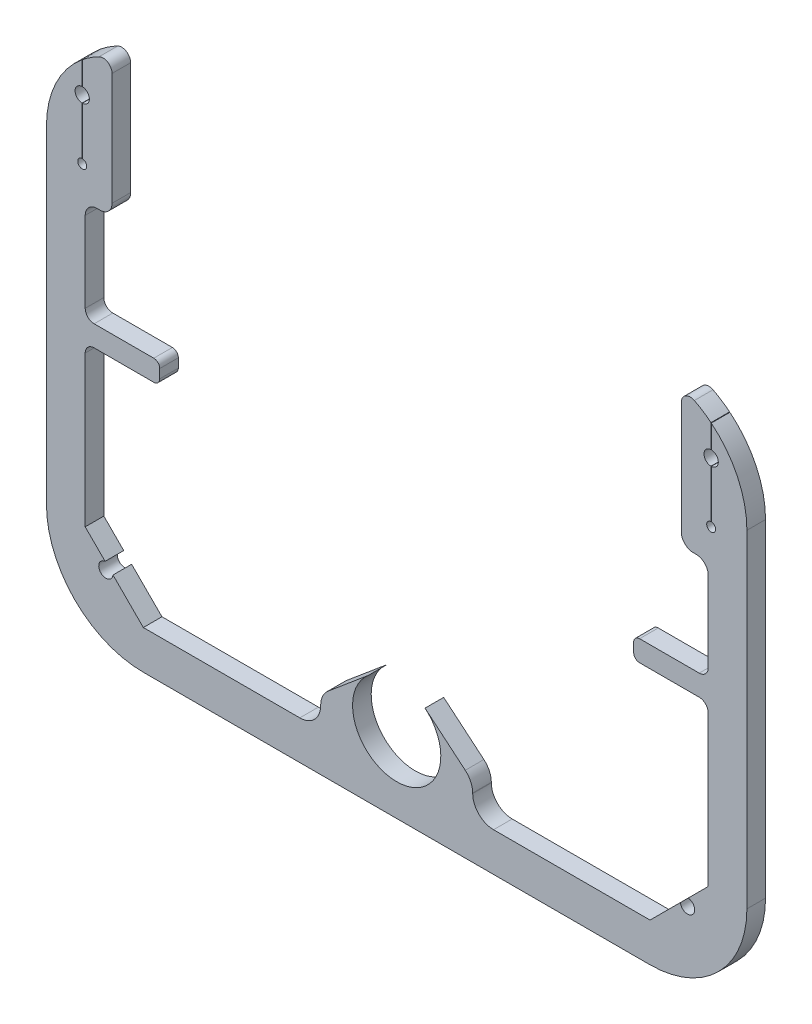
SolidWorks part; units mm, degrees
material "Delrin 2700 NC010, Low Viscosity Acetal Copolymer (SS)"
ref_plane "Front Plane" through (0, 0, 0) normal (0, 0, 1) x (1, 0, 0)
ref_plane "Top Plane" through (0, 0, 0) normal (0, 1, 0) x (1, 0, 0)
ref_plane "Right Plane" through (0, 0, 0) normal (1, 0, 0) x (0, 0, -1)
sketch "Sketch1" plane through (0, 0, 0) normal (0, 0, 1) x (1, 0, 0)
  line L0 (-21.59, -18.923) -> (-9.6321, -18.923)
  line L1 (21.59, 22.225) -> (-21.59, 22.225)
  line L2 (29.845, 13.97) -> (29.845, -13.97)
  line L3 (21.59, -22.225) -> (-21.59, -22.225)
  line L4 (-29.845, 13.97) -> (-29.845, -13.97)
  line L5 (29.845, 22.225) -> (-29.845, -22.225) construction
  line L6 (29.845, -22.225) -> (-29.845, 22.225) construction
  line L7 (9.6321, -18.923) -> (21.59, -18.923)
  line L8 (-26.543, -0.381) -> (-20.193, -0.381)
  line L9 (26.543, 1.397) -> (20.193, 1.397)
  line L10 (-26.543, 10.033) -> (-26.543, -13.97)
  line L11 (-1000, 0) -> (49000, 0) construction
  line L12 (-26.543, 0) -> (-26.543, -1.27)
  line L13 (26.543, 10.033) -> (26.543, -13.97)
  line L14 (21.59, 18.923) -> (-21.59, 18.923)
  line L15 (26.543, 1.397) -> (26.543, -0.381)
  line L16 (26.543, -0.381) -> (20.193, -0.381)
  line L17 (20.193, 1.397) -> (20.193, -0.381)
  line L18 (0, 18.923) -> (0, -18.415) construction
  line L19 (-20.193, 1.397) -> (-20.193, -0.381)
  line L20 (-26.543, 1.397) -> (-20.193, 1.397)
  line L21 (2.4164, -12.8683) -> (9.6321, -18.923)
  line L22 (-2.4164, -12.8683) -> (-9.6321, -18.923)
  line L23 (21.59, 18.923) -> (21.59, 10.033)
  line L24 (-21.59, 18.923) -> (-21.59, 10.033)
  line L25 (26.543, -13.97) -> (21.59, -18.923)
  line L26 (-21.59, 10.033) -> (-26.543, 10.033)
  line L27 (-26.543, -13.97) -> (-21.59, -18.923)
  line L28 (21.59, 10.033) -> (26.543, 10.033)
  line L29 (-26.543, 13.97) -> (-26.543, -13.97) construction
  line L31 (26.543, 13.97) -> (26.543, -13.97) construction
  line L36 (21.59, -18.923) -> (-21.59, -18.923) construction
  arc A0 (-2.4164, -12.8683) -> (2.4164, -12.8683) centre (0, -15.748) ccw
  arc A1 (-21.59, 22.225) -> (-29.845, 13.97) centre (-21.59, 13.97) ccw
  arc A2 (21.59, 22.225) -> (29.845, 13.97) centre (21.59, 13.97) cw
  arc A3 (29.845, -13.97) -> (21.59, -22.225) centre (21.59, -13.97) cw
  arc A4 (-21.59, -22.225) -> (-29.845, -13.97) centre (-21.59, -13.97) cw
  arc A13 (-21.59, -18.923) -> (-26.543, -13.97) centre (-21.59, -13.97) cw construction
  arc A14 (26.543, -13.97) -> (21.59, -18.923) centre (21.59, -13.97) cw construction
  arc A17 (21.59, 18.923) -> (26.543, 13.97) centre (21.59, 13.97) cw construction
  arc A18 (-21.59, 18.923) -> (-26.543, 13.97) centre (-21.59, 13.97) ccw construction
  point P0 (0, 0)
  dimension "D4" = 7.5184
  dimension "D6" = 8.255
  dimension "D7" = 8.255
  dimension "D8" = 8.255
  dimension "D9" = 8.255
  dimension "D5" = 8.89
  dimension "D1" = 59.69
  dimension "D2" = 44.45
  dimension "D10" = 3.302
  dimension "D3" = 3.175
  dimension "D13" = 15.748
  dimension "D14" = 1.778
  dimension "D15" = 21.844
  dimension "D16" = 6.35
extrude "Boss-Extrude1" add sketch "Sketch1" along normal blind 1.5875 contours A4 L3 A3 L2 A2 L1 A1 L4 L25 L7 L21 A0 L22 L0 L27 L10 L14 L13 | L9 L17 L16 L13 | L20 L10 L8 L19 region at (-23.368, 0.508, 0) region at (23.368, 0.508, 0) region at (26.9009, 19.2809, 0)
sketch "Sketch2" plane through (0, 0, 1.5875) normal (0, 0, 1) x (1, 0, 0)
  line L0 (-21.59, 10.033) -> (-26.543, 10.033) construction
  line L1 (-9.6321, -18.923) -> (-6.477, -18.923)
  line L2 (-9.6321, -18.923) -> (-9.6321, -16.2756)
  line L3 (-9.6321, -16.2756) -> (-6.477, -16.2756)
  line L4 (-6.477, -18.923) -> (-6.477, -16.2756)
  line L5 (0, -1000) -> (0, 49000) construction
  line L6 (9.6321, -18.923) -> (9.6321, -16.2756)
  line L7 (9.6321, -16.2756) -> (6.477, -16.2756)
  line L8 (6.477, -18.923) -> (6.477, -16.2756)
  line L9 (9.6321, -18.923) -> (6.477, -18.923)
  line L10 (-29.845, 13.97) -> (-29.845, -13.97) construction
  line L11 (-21.59, 18.923) -> (21.59, 18.923)
  line L12 (-24.257, 10.033) -> (-24.257, 22.225)
  line L13 (-24.257, 22.225) -> (24.257, 22.225)
  line L14 (24.257, 10.033) -> (24.257, 22.225)
  line L16 (21.59, 18.923) -> (-21.59, 18.923) construction
  line L17 (-2.4164, -12.8683) -> (-9.6321, -18.923) construction
  line L18 (21.59, 22.225) -> (-21.59, 22.225) construction
  line L19 (21.59, 18.923) -> (-21.59, 18.923) construction
  line L22 (-21.59, 18.923) -> (-21.59, 10.033) construction
  line L23 (21.59, 10.033) -> (26.543, 10.033) construction
  line L24 (21.59, 18.923) -> (21.59, 10.033) construction
  line L25 (-21.59, 18.923) -> (-21.59, 10.033)
  line L26 (-21.59, 10.033) -> (-24.257, 10.033)
  line L27 (21.59, 10.033) -> (24.257, 10.033)
  line L28 (21.59, 18.923) -> (21.59, 10.033)
  point P25 (0, 22.225)
  dimension "D1" = 6.477
  dimension "D2" = 5.588
extrude "Cut-Extrude1" cut sketch "Sketch2" against normal up to next
fillet "Fillet1" radius 1.778 4 edges at (6.477, -18.923, 0.7937) (6.477, -16.2756, 0.7937) (-6.477, -18.923, 0.7937) (-6.477, -16.2756, 0.7937)
fillet "Fillet2" radius 0.762 2 edges at (24.257, 21.7823, 0.7937) (-24.257, 21.7823, 0.7937)
fillet "Fillet3" radius 0.762 4 edges at (-26.543, -0.381, 0.7937) (26.543, -0.381, 0.7937) (26.543, 1.397, 0.7937) (-26.543, 1.397, 0.7937)
sketch "Sketch3" plane through (0, 0, 1.5875) normal (0, 0, 1) x (1, 0, 0)
  line L0 (-25.019, -16.51) -> (-24.7804, -16.2714) construction
  line L1 (21.59, -22.225) -> (-21.59, -22.225) construction
  line L2 (-26.543, -13.97) -> (-21.59, -18.923) construction
  line L3 (24.7804, -16.2714) -> (25.019, -16.51) construction
  circle A0 centre (-25.019, -16.51) radius 0.6096 construction
  circle A1 centre (-25.019, 16.256) radius 0.6096 construction
  circle A2 centre (25.019, 16.256) radius 0.6096 construction
  circle A3 centre (25.019, -16.51) radius 0.6096 construction
  circle A4 centre (-25.019, -16.51) radius 0.6096 construction
  circle A5 centre (-25.019, 16.256) radius 0.6096 construction
  circle A6 centre (25.019, 16.256) radius 0.6096 construction
  circle A7 centre (25.019, -16.51) radius 0.6096 construction
  circle A8 centre (-26.797, 17.78) radius 0.6096
  circle A9 centre (-24.7804, -16.2714) radius 0.6096
  circle A10 centre (26.797, 17.78) radius 0.6096
  circle A11 centre (24.7804, -16.2714) radius 0.6096
  dimension "D1" = 1.524
  dimension "D2" = 1.778
  dimension "D3" = 135
  dimension "D4" = 0.381
  dimension "D5" = 1.778
  dimension "D6" = 135
extrude "Cut-Extrude2" cut sketch "Sketch3" against normal up to surface (1.5875 mm away) up to face at (0, -3.8116, 0)
sketch "Sketch5" plane through (0, 0, 1.5875) normal (0, 0, 1) x (1, 0, 0)
  line L0 (-26.797, 19.7924) -> (-26.797, 9.1554) construction
  line L1 (-26.8097, 20.3859) -> (-26.7843, 20.3859)
  line L2 (-26.8097, 20.3859) -> (-26.8097, 13.0808)
  line L3 (-26.7843, 20.3859) -> (-26.7843, 13.0808)
  line L4 (-26.797, 17.78) -> (-26.797, 17.1704) construction
  arc A0 (-26.8097, 13.0808) -> (-26.7843, 13.0808) centre (-26.797, 12.7) ccw
  circle A1 centre (-26.797, 17.78) radius 0.6096 construction
  arc A2 (-25.3677, 21.3099) -> (-29.845, 13.97) centre (-21.59, 13.97) ccw construction
  dimension "D2" = 0.762
  dimension "D3" = 5.08
  dimension "D1" = 0.0254
extrude "Cut-Extrude3" cut sketch "Sketch5" against normal through all
fillet "Fillet4" radius 1.016 4 edges at (-26.543, 10.033, 0.7937) (26.543, 10.033, 0.7937) (24.257, 10.033, 0.7937) (-24.257, 10.033, 0.7937)
mirror "Mirror1" about plane through (0, 0, 0) normal (1, 0, 0) of "Cut-Extrude3"
fillet "Fillet5" radius 0.508 4 edges at (20.193, -0.381, 0.7937) (20.193, 1.397, 0.7937) (-20.193, -0.381, 0.7937) (-20.193, 1.397, 0.7937)
equation "\"SnapInRodSlotSize\"=0.02"
